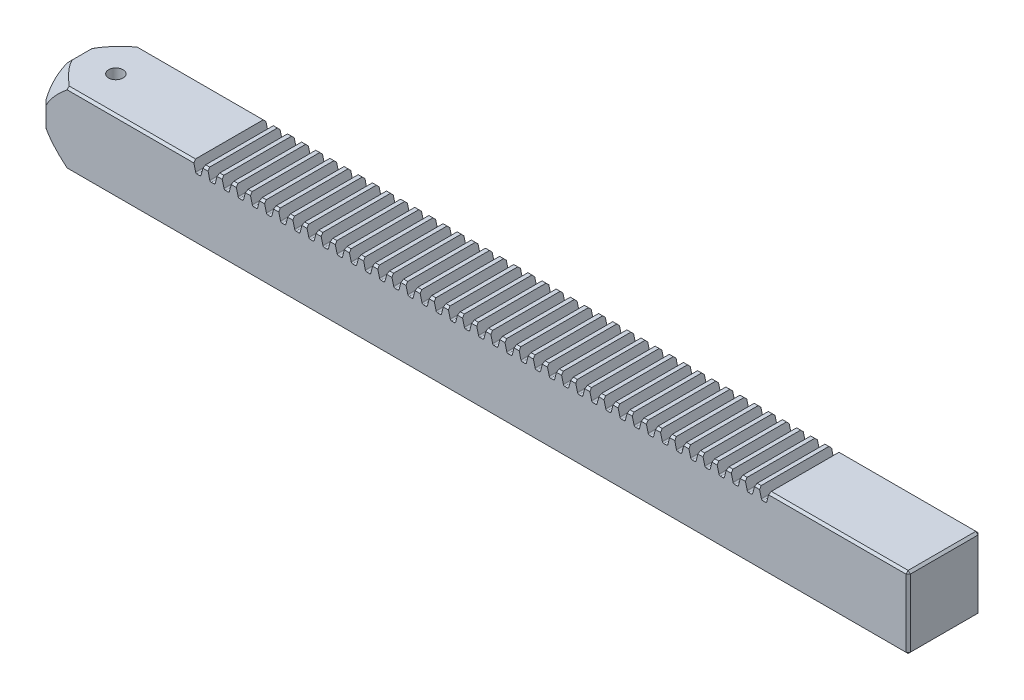
SolidWorks part; units mm, degrees
ref_plane "Front Plane" through (0, 0, 0) normal (0, 0, 1) x (1, 0, 0)
ref_plane "Top Plane" through (0, 0, 0) normal (0, 1, 0) x (1, 0, 0)
ref_plane "Right Plane" through (0, 0, 0) normal (1, 0, 0) x (0, 0, -1)
sketch "Sketch2" plane through (0, 0, 0) normal (1, 0, 0) x (0, 0, -1)
  line L1 (12.7, -12.7) -> (-12.7, -12.7)
  line L2 (12.7, -12.7) -> (12.7, 12.7)
  line L3 (12.7, 12.7) -> (-12.7, 12.7)
  line L4 (-12.7, -12.7) -> (-12.7, 12.7)
  line L5 (12.7, -12.7) -> (-12.7, 12.7) construction
  line L6 (12.7, 12.7) -> (-12.7, -12.7) construction
  point P0 (0, 0)
  dimension "D1" = 25.4
  dimension "D2" = 25.4
extrude "Boss-Extrude1" add sketch "Sketch2" along normal blind 304.8
chamfer "Chamfer1" distance 0.762 angle 45 12 edges at (304.8, -12.7, 0) (0, -12.7, 0) (152.4, -12.7, -12.7) (304.8, 0, -12.7) (0, 0, -12.7) (304.8, 0, 12.7) (152.4, -12.7, 12.7) (0, 0, 12.7) (152.4, 12.7, -12.7) (304.8, 12.7, 0) (152.4, 12.7, 12.7) (0, 12.7, 0)
sketch "Sketch3" plane through (0, 0, 12.7) normal (0, 0, 1) x (1, 0, 0)
  line L0 (252.2138, 12.7) -> (253.0455, 9.4842)
  line L1 (0.762, 12.7) -> (304.038, 12.7) construction
  line L2 (253.5373, 9.1034) -> (254.4627, 9.1034)
  line L3 (254.9545, 9.4842) -> (255.7862, 12.7)
  line L4 (255.7862, 12.7) -> (252.2138, 12.7)
  line L5 (254, 9.1034) -> (254, 22.4475) construction
  line L6 (252.6297, 11.0921) -> (255.3703, 11.0921) construction
  line L7 (304.8, 11.938) -> (304.8, -11.938) construction
  arc A0 (253.0455, 9.4842) -> (253.5373, 9.1034) centre (253.5373, 9.6114) ccw
  arc A1 (254.4627, 9.1034) -> (254.9545, 9.4842) centre (254.4627, 9.6114) ccw
  dimension "D3" = 1.6079
  dimension "D4" = 0.508
  dimension "D1" = 3.5966
  dimension "D2" = 14.5
  dimension "D5" = 2.7407
  dimension "D6" = 50.8
extrude "Cut-Extrude1" cut sketch "Sketch3" against normal through all
pattern_linear "LPattern1" count 41 spacing 4.9873 along (-1, 0, 0) of "Cut-Extrude1"
hole_wizard "9/16 (0.5625) Diameter Hole1" positions "Sketch4" profile "Sketch5" hole size "9/16" standard "ANSI Inch"
sketch "Sketch4" plane through (0, 0, 0) normal (-1, 0, 0) x (0, 0, 1)
  point P0 (0, 0)
sketch "Sketch5" plane through (0, 0, 0) normal (0, 1, 0) x (0, 0, 1)
  line L0 (0, 0) -> (0, 29.6924)
  line L1 (0, 29.6924) -> (7.1437, 25.4)
  line L2 (7.1437, 25.4) -> (7.1437, 0)
  line L5 (7.1437, 0) -> (0, 0)
  line L10 (0, 29.6924) -> (-7.1438, 25.4) construction
  line L11 (0, -6.35) -> (0, 107.95) construction
  dimension "Hole Dia." = 14.2875
  dimension "Hole Depth" = 25.4
  dimension "Drill Angle" = 118
hole_wizard "1/4-20 Tapped Hole1" positions "Sketch6" profile "Sketch7" tap size "1/4-20" standard "ANSI Inch" end condition up to next
sketch "Sketch6" plane through (0, 12.7, 0) normal (0, 1, 0) x (1, 0, 0)
  line L0 (0, -11.938) -> (0, 11.938) construction
  point P0 (12.7, 0)
  dimension "D1" = 12.7
sketch "Sketch7" plane through (12.7, 12.7, 0) normal (1, 0, 0) x (0, 0, 1)
  line L0 (0, 0) -> (0, 5.5563)
  line L1 (0, 5.5563) -> (2.5527, 5.5563)
  line L2 (2.5527, 5.5563) -> (2.5527, 0)
  line L5 (2.5527, 0) -> (0, 0)
  line L11 (0, -6.35) -> (0, 107.95) construction
  dimension "Thru Tap Drill Dia." = 5.1054
  dimension "Thru Tap Drill Depth" = 5.5563
cosmetic thread "Hole Thread1" parameters "D2"=6.35
sketch "Sketch8" plane through (0, 0, 0) normal (0, 0, 1) x (1, 0, 0)
  line L0 (0, 12.7) -> (0, 17.78)
  line L1 (0, 17.78) -> (8.7988, 17.78)
  line L2 (8.7988, 17.78) -> (0, 12.7)
  line L3 (0, 0) -> (13.0384, 0) construction
  line L4 (0.762, 12.7) -> (52.7222, 12.7) construction
  dimension "D1" = 30
  dimension "D2" = 5.08
revolve "Cut-Revolve1" cut sketch "Sketch8" angle 360 about L3
